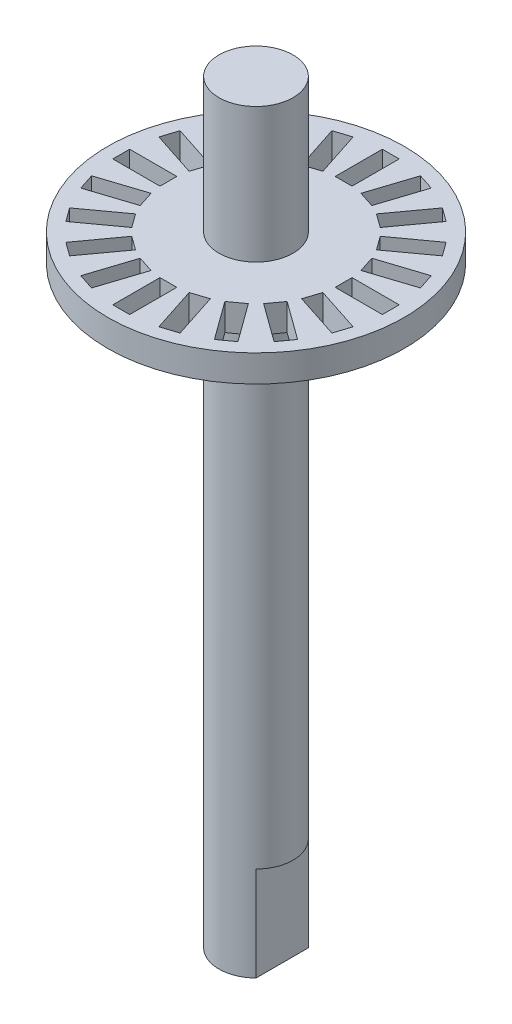
SolidWorks part; units mm, degrees
ref_plane "前视基准面" through (0, 0, 0) normal (0, 0, 1) x (1, 0, 0)
ref_plane "上视基准面" through (0, 0, 0) normal (0, 1, 0) x (1, 0, 0)
ref_plane "右视基准面" through (0, 0, 0) normal (1, 0, 0) x (0, 0, -1)
sketch "草图1" plane through (0, 0, 0) normal (0, 1, 0) x (1, 0, 0)
  circle A0 centre (0, 0) radius 2.75
  dimension "D1" = 5.5
extrude "凸台-拉伸1" add sketch "草图1" along normal blind 49
sketch "草图2" plane through (0, 0, 0) normal (0, -1, 0) x (1, 0, 0)
  line L0 (0, 0) -> (0, -4.8851) construction
  line L2 (-1.95, 1.9391) -> (-1.95, -1.9391)
  line L4 (1.95, 1.9391) -> (1.95, -1.9391)
  arc A0 (-1.95, -1.9391) -> (1.95, -1.9391) centre (0, 0) ccw
  arc A1 (1.95, 1.9391) -> (-1.95, 1.9391) centre (0, 0) ccw
  dimension "D1" = 5.5
  dimension "D2" = 3.9
extrude "凸台-拉伸2" add sketch "草图2" along normal blind 7
sketch "草图6" plane through (0, 49, 0) normal (0, 1, 0) x (1, 0, 0)
  line L2 (0, 11) -> (0, 0) construction
  line L3 (2.4958, 9.7037) -> (3.6846, 9.3174)
  line L42 (-0.625, 10) -> (0.625, 10)
  line L43 (-0.625, 10) -> (-0.625, 6.5)
  line L44 (-0.625, 6.5) -> (0.625, 6.5)
  line L45 (0.625, 10) -> (0.625, 6.5)
  line L46 (2.4958, 9.7037) -> (1.4142, 6.375)
  line L47 (1.4142, 6.375) -> (2.603, 5.9887)
  line L48 (3.6846, 9.3174) -> (2.603, 5.9887)
  line L49 (5.3722, 8.4575) -> (6.3835, 7.7228)
  line L50 (5.3722, 8.4575) -> (3.315, 5.626)
  line L51 (3.315, 5.626) -> (4.3262, 4.8912)
  line L52 (6.3835, 7.7228) -> (4.3262, 4.8912)
  line L53 (7.7228, 6.3835) -> (8.4575, 5.3722)
  line L54 (7.7228, 6.3835) -> (4.8912, 4.3262)
  line L55 (4.8912, 4.3262) -> (5.626, 3.315)
  line L56 (8.4575, 5.3722) -> (5.626, 3.315)
  line L57 (9.3174, 3.6846) -> (9.7037, 2.4958)
  line L58 (9.3174, 3.6846) -> (5.9887, 2.603)
  line L59 (5.9887, 2.603) -> (6.375, 1.4142)
  line L60 (9.7037, 2.4958) -> (6.375, 1.4142)
  line L61 (10, 0.625) -> (10, -0.625)
  line L62 (10, 0.625) -> (6.5, 0.625)
  line L63 (6.5, 0.625) -> (6.5, -0.625)
  line L64 (10, -0.625) -> (6.5, -0.625)
  line L65 (9.7037, -2.4958) -> (9.3174, -3.6846)
  line L66 (9.7037, -2.4958) -> (6.375, -1.4142)
  line L67 (6.375, -1.4142) -> (5.9887, -2.603)
  line L68 (9.3174, -3.6846) -> (5.9887, -2.603)
  line L69 (8.4575, -5.3722) -> (7.7228, -6.3835)
  line L70 (8.4575, -5.3722) -> (5.626, -3.315)
  line L71 (5.626, -3.315) -> (4.8912, -4.3262)
  line L72 (7.7228, -6.3835) -> (4.8912, -4.3262)
  line L73 (6.3835, -7.7228) -> (5.3722, -8.4575)
  line L74 (6.3835, -7.7228) -> (4.3262, -4.8912)
  line L75 (4.3262, -4.8912) -> (3.315, -5.626)
  line L76 (5.3722, -8.4575) -> (3.315, -5.626)
  line L77 (3.6846, -9.3174) -> (2.4958, -9.7037)
  line L78 (3.6846, -9.3174) -> (2.603, -5.9887)
  line L79 (2.603, -5.9887) -> (1.4142, -6.375)
  line L80 (2.4958, -9.7037) -> (1.4142, -6.375)
  line L81 (0.625, -10) -> (-0.625, -10)
  line L82 (0.625, -10) -> (0.625, -6.5)
  line L83 (0.625, -6.5) -> (-0.625, -6.5)
  line L84 (-0.625, -10) -> (-0.625, -6.5)
  line L85 (-2.4958, -9.7037) -> (-3.6846, -9.3174)
  line L86 (-2.4958, -9.7037) -> (-1.4142, -6.375)
  line L87 (-1.4142, -6.375) -> (-2.603, -5.9887)
  line L88 (-3.6846, -9.3174) -> (-2.603, -5.9887)
  line L89 (-5.3722, -8.4575) -> (-6.3835, -7.7228)
  line L90 (-5.3722, -8.4575) -> (-3.315, -5.626)
  line L91 (-3.315, -5.626) -> (-4.3262, -4.8912)
  line L92 (-6.3835, -7.7228) -> (-4.3262, -4.8912)
  line L93 (-7.7228, -6.3835) -> (-8.4575, -5.3722)
  line L94 (-7.7228, -6.3835) -> (-4.8912, -4.3262)
  line L95 (-4.8912, -4.3262) -> (-5.626, -3.315)
  line L96 (-8.4575, -5.3722) -> (-5.626, -3.315)
  line L97 (-9.3174, -3.6846) -> (-9.7037, -2.4958)
  line L98 (-9.3174, -3.6846) -> (-5.9887, -2.603)
  line L99 (-5.9887, -2.603) -> (-6.375, -1.4142)
  line L100 (-9.7037, -2.4958) -> (-6.375, -1.4142)
  line L101 (-10, -0.625) -> (-10, 0.625)
  line L102 (-10, -0.625) -> (-6.5, -0.625)
  line L103 (-6.5, -0.625) -> (-6.5, 0.625)
  line L104 (-10, 0.625) -> (-6.5, 0.625)
  line L105 (-9.7037, 2.4958) -> (-9.3174, 3.6846)
  line L106 (-9.7037, 2.4958) -> (-6.375, 1.4142)
  line L107 (-6.375, 1.4142) -> (-5.9887, 2.603)
  line L108 (-9.3174, 3.6846) -> (-5.9887, 2.603)
  line L109 (-8.4575, 5.3722) -> (-7.7228, 6.3835)
  line L110 (-8.4575, 5.3722) -> (-5.626, 3.315)
  line L111 (-5.626, 3.315) -> (-4.8912, 4.3262)
  line L112 (-7.7228, 6.3835) -> (-4.8912, 4.3262)
  line L113 (-6.3835, 7.7228) -> (-5.3722, 8.4575)
  line L114 (-6.3835, 7.7228) -> (-4.3262, 4.8912)
  line L115 (-4.3262, 4.8912) -> (-3.315, 5.626)
  line L116 (-5.3722, 8.4575) -> (-3.315, 5.626)
  line L117 (-3.6846, 9.3174) -> (-2.4958, 9.7037)
  line L118 (-3.6846, 9.3174) -> (-2.603, 5.9887)
  line L119 (-2.603, 5.9887) -> (-1.4142, 6.375)
  line L120 (-2.4958, 9.7037) -> (-1.4142, 6.375)
  circle A0 centre (0, 0) radius 11
  point P88 (0, 0)
  dimension "D1" = 22
  dimension "D3" = 10
  dimension "D4" = 6.5
  dimension "D2" = 1.25
extrude "凸台-拉伸4" add sketch "草图6" along normal blind 2 from offset 12 offset against normal yes
